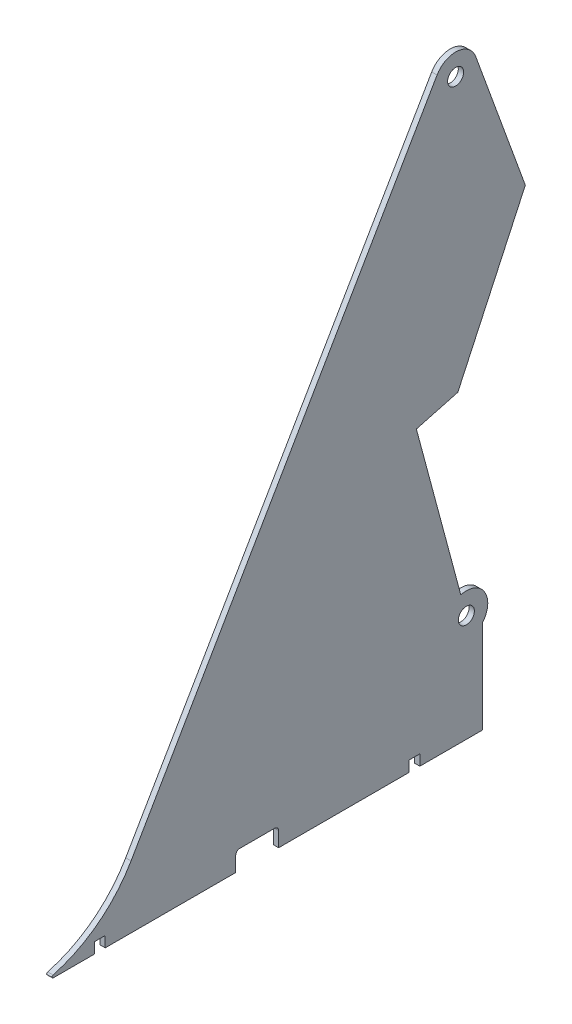
SolidWorks part; units mm, degrees
ref_plane "Front Plane" through (0, 0, 0) normal (0, 0, 1) x (1, 0, 0)
ref_plane "Top Plane" through (0, 0, 0) normal (0, 1, 0) x (1, 0, 0)
ref_plane "Right Plane" through (0, 0, 0) normal (1, 0, 0) x (0, 0, -1)
sketch "Sketch1" plane through (0, 0, 0) normal (1, 0, 0) x (0, 0, -1)
  line L0 (0, 0) -> (0, 55.0997)
  line L6 (-39.108, 173.9053) -> (-14.5735, 180.4793)
  line L7 (-14.5735, 180.4793) -> (25.4, 266.7)
  line L8 (25.4, 266.7) -> (-3.9421, 347.247)
  line L9 (-26.861, 349.2717) -> (-208.0116, 36.9339)
  line L10 (-254, 0) -> (0, 0)
  line L12 (-254.2054, 1.5605) -> (-207.9989, 13.9415) construction
  line L13 (-39.108, 173.9053) -> (-12.812, 75.7673)
  line L14 (-12.812, 75.7673) -> (13.738, 82.8813) construction
  arc A0 (-3.9421, 347.247) -> (-26.861, 349.2717) centre (-15.875, 342.9) ccw
  arc A1 (-254, 0) -> (-254.2054, 1.5605) centre (-254, 0.7937) cw
  arc A2 (-254.2054, 1.5605) -> (-208.0116, 36.9339) centre (-273.9274, 75.164) ccw
  arc A3 (0, 55.0997) -> (-12.812, 75.7673) centre (-9.525, 63.5) ccw
  dimension "D2" = 12.7
  dimension "D6" = 0.7937
  dimension "D7" = 76.2
  dimension "D12" = 12.7
  dimension "D1" = 15.875
  dimension "D3" = 342.9
  dimension "D4" = 25.4
  dimension "D5" = 101.6
  dimension "D8" = 254
  dimension "D9" = 15
  dimension "D10" = 9.525
  dimension "D11" = 63.5
  dimension "D13" = 76.2
  dimension "D14" = 25.4
  dimension "D15" = 15
extrude "Boss-Extrude1" add sketch "Sketch1" along normal blind 3.175
sketch "Sketch2" plane through (3.175, 0, 0) normal (1, 0, 0) x (0, 0, -1)
  line L16 (-146.05, 8.7909) -> (-146.05, -0.3034) construction
  line L17 (-123.0376, 11.1785) -> (-143.6624, 11.1785) construction
  line L18 (-120.65, -0.3034) -> (-120.65, 8.7909) construction
  line L19 (-146.05, 8.7909) -> (-146.05, 0)
  line L20 (-123.0376, 11.1785) -> (-143.6624, 11.1785)
  line L21 (-120.65, 0) -> (-120.65, 8.7909)
  line L23 (-37.0504, 0) -> (-37.0504, 6.35) construction
  line L24 (-43.4004, 0) -> (-37.0504, 0) construction
  line L25 (-146.05, 0) -> (-120.65, 0)
  line L26 (-254, 0) -> (0, 0) construction
  line L27 (-43.4004, 6.35) -> (-43.4004, 0) construction
  line L28 (-37.0504, 6.35) -> (-43.4004, 6.35) construction
  line L29 (-37.0504, 0) -> (-37.0504, 6.35)
  line L30 (-43.4004, 0) -> (-37.0504, 0)
  line L31 (-43.4004, 6.35) -> (-43.4004, 0)
  line L32 (-37.0504, 6.35) -> (-43.4004, 6.35)
  line L33 (-223.2996, 0) -> (-223.2996, 6.35) construction
  line L34 (-229.6496, 0) -> (-223.2996, 0) construction
  line L35 (-229.6496, 6.35) -> (-229.6496, 0) construction
  line L36 (-223.2996, 6.35) -> (-229.6496, 6.35) construction
  line L37 (-223.2996, 0) -> (-223.2996, 6.35)
  line L38 (-229.6496, 0) -> (-223.2996, 0)
  line L39 (-229.6496, 6.35) -> (-229.6496, 0)
  line L40 (-223.2996, 6.35) -> (-229.6496, 6.35)
  arc A0 (-143.6624, 11.1785) -> (-146.05, 8.7909) centre (-143.6624, 8.7909) ccw construction
  arc A1 (-120.65, 8.7909) -> (-123.0376, 11.1785) centre (-123.0376, 8.7909) ccw construction
  arc A2 (-143.6624, 11.1785) -> (-146.05, 8.7909) centre (-143.6624, 8.7909) ccw
  arc A3 (-120.65, 8.7909) -> (-123.0376, 11.1785) centre (-123.0376, 8.7909) ccw
extrude "Cut-Extrude1" cut sketch "Sketch2" against normal through all
sketch "Sketch3" plane through (3.175, 0, 0) normal (1, 0, 0) x (0, 0, -1)
  point P0 (-15.875, 342.9)
  point P4 (-9.525, 63.5)
hole_wizard "3/8 Clearance Hole1" positions "Sketch3" profile "Sketch4" hole size "3/8" standard "ANSI Inch" end condition up to next
sketch "Sketch4" plane through (3.175, 342.9, 15.875) normal (0, 1, 0) x (0, 0, -1)
  line L0 (0, 0) -> (0, 3.175)
  line L1 (0, 3.175) -> (4.7625, 3.175)
  line L2 (4.7625, 3.175) -> (4.7625, 0)
  line L5 (4.7625, 0) -> (0, 0)
  line L11 (0, -6.35) -> (0, 107.95) construction
  dimension "Thru Hole Dia." = 9.525
  dimension "Thru Hole Depth" = 3.175
sketch "Sketch5" plane through (3.175, 0, 0) normal (1, 0, 0) x (0, 0, -1)
  line L0 (-9.525, 63.5) -> (25.2029, 26.4242)
  line L1 (25.2029, 26.4242) -> (24.793, 13.8877)
  line L2 (20.8619, 31.0587) -> (-25.3801, 19.6651)
  line L3 (-15.875, 19.05) -> (-25.3801, 19.6651)
  line L4 (0, 0) -> (0, 55.0997) construction
  line L5 (-15.875, 19.05) -> (-30.1872, 6.4776)
  line L6 (-30.1872, 6.4776) -> (-54.7505, 169.5016)
  line L7 (50.8, 0) -> (50.8, 73.5762) construction
  dimension "D1" = 44.45
  dimension "D2" = 50.8
  dimension "D3" = 45
  dimension "D4" = 60.325
  dimension "D5" = 19.05
  dimension "D6" = 15.875
  dimension "D7" = 9.525
  dimension "D8" = 47.625
  dimension "D9" = 19.05
  dimension "D10" = 45
  dimension "D11" = 50.8
